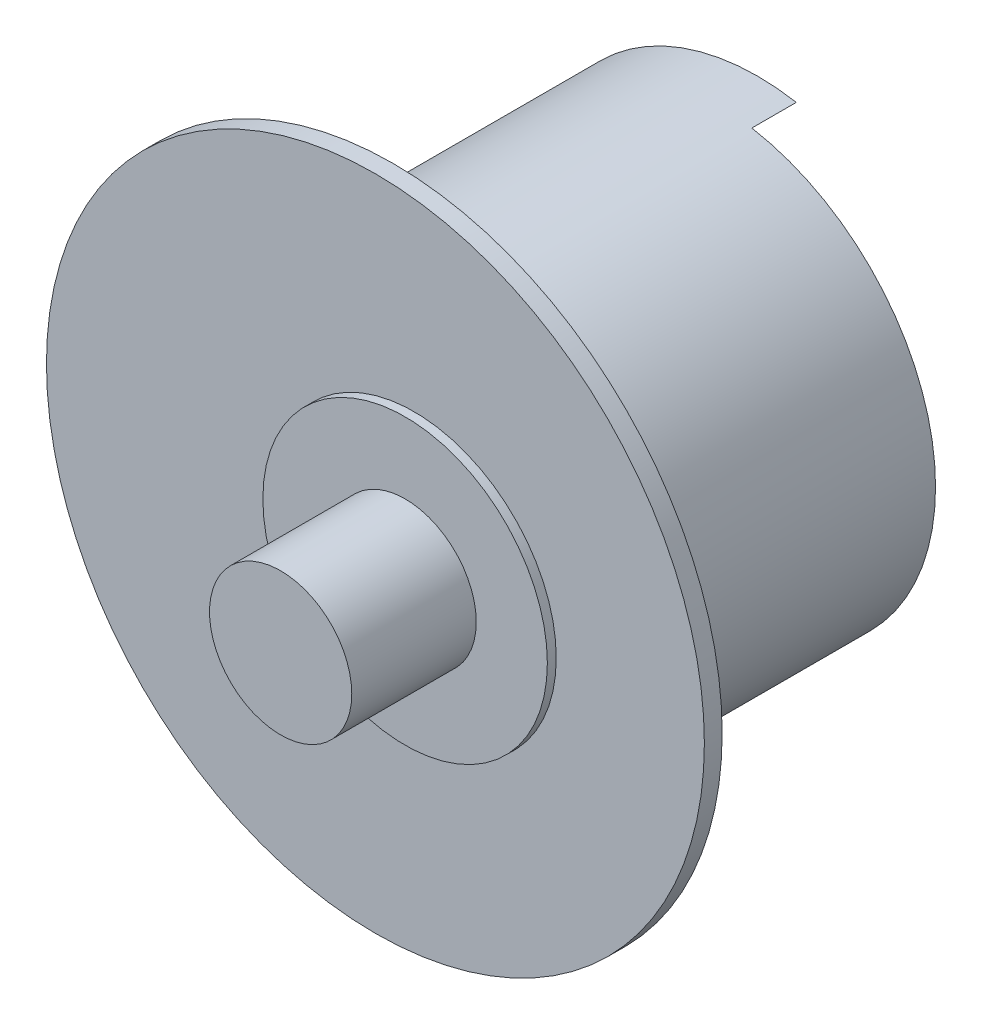
SolidWorks part; units mm, degrees
material "PETG"
ref_plane "Front Plane" through (0, 0, 0) normal (0, 0, 1) x (1, 0, 0)
ref_plane "Top Plane" through (0, 0, 0) normal (0, 1, 0) x (1, 0, 0)
ref_plane "Right Plane" through (0, 0, 0) normal (1, 0, 0) x (0, 0, -1)
sketch "Sketch1" plane through (0, 0, 0) normal (0, 0, 1) x (1, 0, 0)
  line L1 (-2, 3.4641) -> (-4, 0)
  line L2 (-4, 0) -> (-2, -3.4641)
  line L3 (-2, -3.4641) -> (2, -3.4641)
  line L4 (2, -3.4641) -> (4, 0)
  line L5 (4, 0) -> (2, 3.4641)
  line L6 (2, 3.4641) -> (-2, 3.4641)
  circle A0 centre (0, 0) radius 4 construction
  circle A1 centre (-2.17, 0) radius 12.5
  circle A2 centre (0, 0) radius 3.4641 construction
  dimension "D1" = 25
  dimension "D2" = 8
  dimension "D3" = 2.17
extrude "Boss-Extrude1" add sketch "Sketch1" along normal blind 13 contours L1 A0 | A1 region at (0, 0, 0)
sketch "Sketch6" plane through (0, 0, 13) normal (0, 0, 1) x (1, 0, 0)
  circle A0 centre (-2.17, 0) radius 12.5
  circle A1 centre (-2.17, 0) radius 12.5 construction
extrude "Boss-Extrude7" add sketch "Sketch6" along normal blind 5
sketch "Sketch3" plane through (0, 0, 18) normal (0, 0, -1) x (-1, 0, 0)
  circle A0 centre (2.17, 0) radius 18.5
  circle A2 centre (2.17, 0) radius 12.5 construction
  dimension "D1" = 37
extrude "Boss-Extrude3" add sketch "Sketch3" against normal blind 1 contours A0 | A0 region at (-2.17, 0, 18)
sketch "Sketch4" plane through (0, 0, 19) normal (0, 0, 1) x (1, 0, 0)
  circle A0 centre (0, 0) radius 8
  dimension "D1" = 16
extrude "Boss-Extrude5" add sketch "Sketch4" along normal blind 0.5
sketch "Sketch5" plane through (0, 0, 19.5) normal (0, 0, 1) x (1, 0, 0)
  circle A0 centre (0, 0) radius 4
  dimension "D1" = 8
extrude "Boss-Extrude6" add sketch "Sketch5" along normal blind 7
sketch "Sketch7" plane through (0, 0, 0) normal (0, 0, -1) x (-1, 0, 0)
  line L0 (0, 12.3102) -> (0, -12.3102) construction
  line L1 (-2.17, 0) -> (2.17, 0) construction
  circle A0 centre (-2.17, 0) radius 12.5 construction
  circle A1 centre (2.17, 0) radius 12.5 construction
  circle A2 centre (2.17, 0) radius 12.5
  arc A3 (0, 12.3102) -> (0, -12.3102) centre (-2.17, 0) cw
extrude "Boss-Extrude8" add sketch "Sketch7" along normal blind 2.5 contours A2 A3 region at (-10.0188, -9.3533, 0)
equation "\"N\"= 21"
equation "\"R\"= 65mm"
equation "\"E\" = ROUND(\"R\" / \"N\" * 0.7, 2)"
equation "\"D3@Sketch1\"=\"E\""
